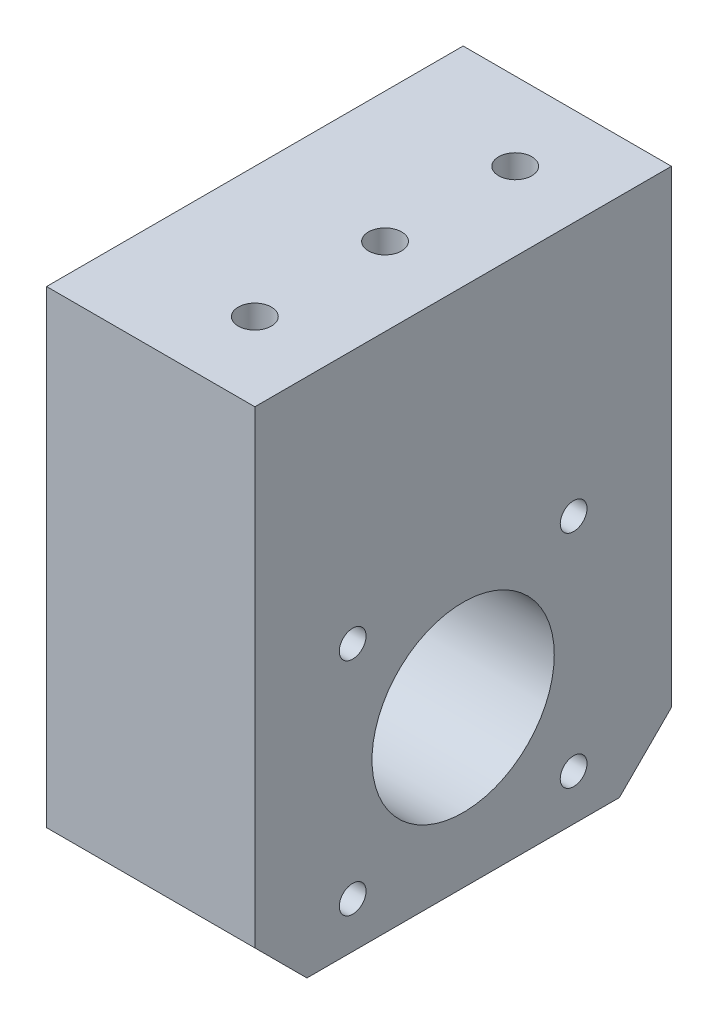
SolidWorks part; units mm, degrees
material "Nylon 6/10"
ref_plane "Front Plane" through (0, 0, 0) normal (0, 0, 1) x (1, 0, 0)
ref_plane "Top Plane" through (0, 0, 0) normal (0, 1, 0) x (1, 0, 0)
ref_plane "Right Plane" through (0, 0, 0) normal (1, 0, 0) x (0, 0, -1)
sketch "Sketch1" plane through (0, 0, 0) normal (1, 0, 0) x (0, 0, -1)
  line L1 (-25.4, -31.75) -> (25.4, -31.75)
  line L2 (-25.4, -31.75) -> (-25.4, 31.75)
  line L3 (-25.4, 31.75) -> (25.4, 31.75)
  line L4 (25.4, -31.75) -> (25.4, 31.75)
  line L5 (-25.4, -31.75) -> (25.4, 31.75) construction
  line L6 (-25.4, 31.75) -> (25.4, -31.75) construction
  point P0 (0, 0)
  dimension "D1" = 50.8
  dimension "D2" = 63.5
extrude "Base" add sketch "Sketch1" along normal blind 25.4
hole_wizard "7/8 (0.875) Diameter Hole1" positions "Sketch3" profile "Sketch2" hole size "7/8" standard "ANSI Inch" end condition through all
sketch "Sketch3" plane through (25.4, 0, 0) normal (1, 0, 0) x (0, 0, -1)
  line L1 (25.4, 31.75) -> (-25.4, 31.75) construction
  line L2 (0, -31.75) -> (0, 31.75) construction
  line L3 (-25.4, -31.75) -> (25.4, -31.75) construction
  point P0 (0, -12.7)
  dimension "D1" = 44.45
sketch "Sketch2" plane through (25.4, -12.7, 0) normal (0, 1, 0) x (0, 0, -1)
  line L0 (0, 0) -> (0, 25.4)
  line L1 (0, 25.4) -> (11.1125, 25.4)
  line L2 (11.1125, 25.4) -> (11.1125, 0)
  line L5 (11.1125, 0) -> (0, 0)
  line L11 (0, -6.35) -> (0, 107.95) construction
  dimension "Thru Hole Dia." = 22.225
  dimension "Thru Hole Depth" = 25.4
hole_wizard "#10-32 Tapped Hole1" positions "Sketch12" profile "Sketch11" tap size "#10-32" standard "ANSI Inch"
sketch "Sketch12" plane through (0, 31.75, 0) normal (0, 1, 0) x (1, 0, 0)
  line L0 (15.875, 25.4) -> (15.875, -25.4) construction
  line L1 (25.4, 25.4) -> (0, 25.4) construction
  line L2 (25.4, -25.4) -> (0, -25.4) construction
  line L3 (25.4, 0) -> (0, 0) construction
  line L4 (25.4, 25.4) -> (25.4, -25.4) construction
  line L5 (0, 25.4) -> (0, -25.4) construction
  point P0 (15.875, 15.875)
  point P2 (15.875, -15.875)
  point P13 (15.875, 0)
  dimension "D1" = 9.525
  dimension "D2" = 9.525
  dimension "D3" = 9.525
sketch "Sketch11" plane through (15.875, 31.75, -15.875) normal (1, 0, 0) x (0, 0, 1)
  line L0 (0, 0) -> (0, 26.6133)
  line L1 (0, 26.6133) -> (2.0193, 25.4)
  line L2 (2.0193, 25.4) -> (2.0193, 0)
  line L5 (2.0193, 0) -> (0, 0)
  line L10 (0, 26.6133) -> (-2.0193, 25.4) construction
  line L11 (0, -6.35) -> (0, 107.95) construction
  dimension "Tap Drill Dia." = 4.0386
  dimension "Tap Drill Depth" = 25.4
  dimension "Drill Angle" = 118
hole_wizard "CBORE for #4 Socket Head Cap Screw1" positions "Sketch14" profile "Sketch13" counterbore size "#4" standard "ANSI Inch" end condition through all
sketch "Sketch14" plane through (0, 0, 0) normal (-1, 0, 0) x (0, 0, 1)
  line L0 (0, 31.75) -> (0, -31.75) construction
  line L1 (-25.4, 31.75) -> (25.4, 31.75) construction
  line L2 (25.4, -31.75) -> (-25.4, -31.75) construction
  line L3 (0, -12.7) -> (-13.4704, 0.7704) construction
  circle A1 centre (0, -12.7) radius 11.1125 construction
  circle A2 centre (0, -12.7) radius 11.1125
  point P0 (-13.4704, 0.7704)
  dimension "D1" = 19.05
  dimension "D2" = 45
sketch "Sketch13" plane through (0, 0.7704, -13.4704) normal (0, 1, 0) x (0, 0, 1)
  line L0 (0, 0) -> (0, 25.4)
  line L1 (0, 25.4) -> (1.6319, 25.4)
  line L3 (1.6319, 25.4) -> (1.632, 2.8448)
  line L4 (1.632, 2.8448) -> (2.7788, 2.8448)
  line L5 (2.7788, 2.8448) -> (2.7788, 0)
  line L7 (2.7788, 0) -> (0, 0)
  line L11 (0, -6.35) -> (0, 107.95) construction
  dimension "Thru Hole Dia." = 3.2639
  dimension "Thru Hole Depth" = 25.4
  dimension "C'Bore Dia." = 5.5575
  dimension "C'Bore Depth" = 2.8448
pattern_circular "CirPattern1" count 4 over 360 about axis through (0, -12.7, 0) along (1, 0, 0) of "CBORE for #4 Socket Head Cap Screw1"
chamfer "Chamfer2" distance 6.35 angle 45 2 edges at (12.7, -31.75, 25.4) (12.7, -31.75, -25.4)
